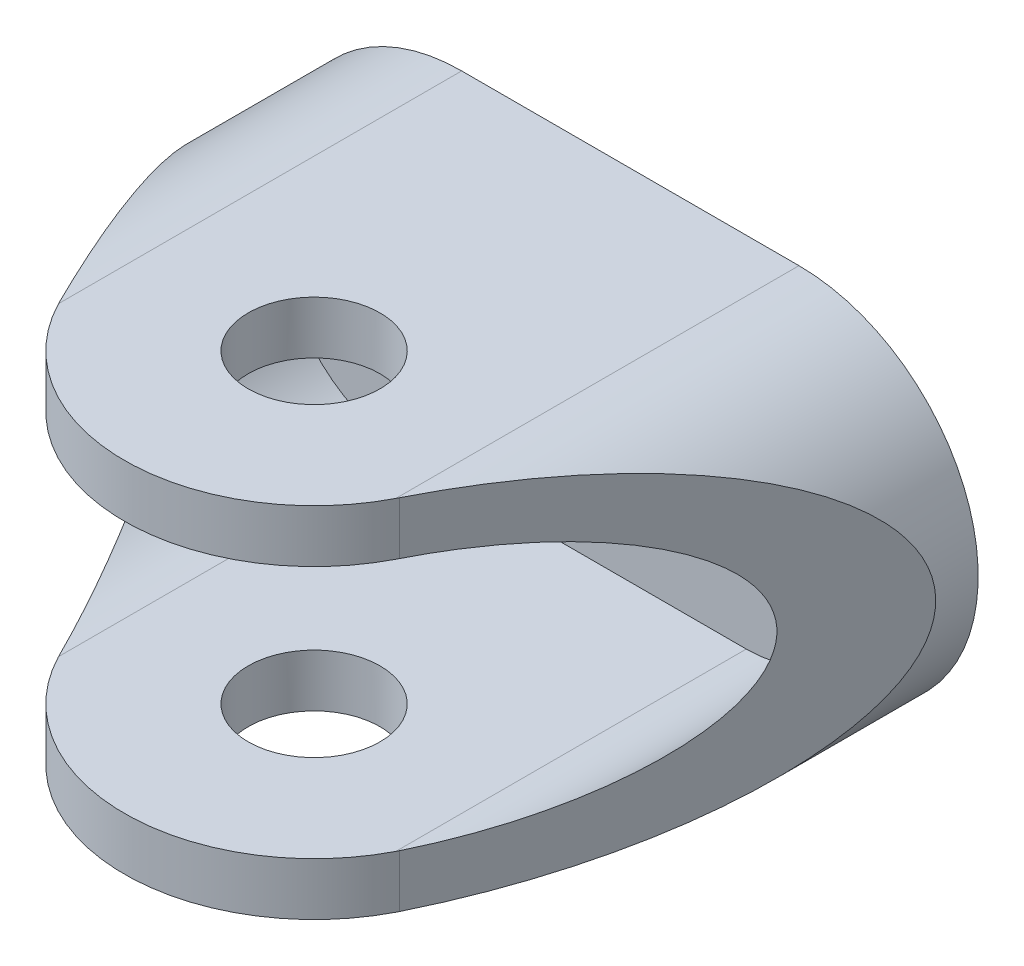
SolidWorks part; units mm, degrees
note: '?' marks a value the reader was unsure of.
material "6061 Alloy"
ref_plane "Front Plane" through (0, 0, 0) normal (0, 0, 1) x (1, 0, 0)
ref_plane "Top Plane" through (0, 0, 0) normal (0, 1, 0) x (1, 0, 0)
ref_plane "Right Plane" through (0, 0, 0) normal (1, 0, 0) x (0, 0, -1)
sketch "Sketch1" plane through (0, 0, 0) normal (0, 1, 0) x (1, 0, 0)
  line L0 (-22.225, -15.875) -> (22.225, -15.875)
  line L1 (-22.225, -15.875) -> (-22.225, 15.875)
  line L2 (22.225, -15.875) -> (22.225, 15.875)
  line L3 (-22.225, 15.875) -> (22.225, 15.875)
  line L4 (-22.225, -15.875) -> (22.225, 15.875) construction
  line L5 (22.225, -15.875) -> (-22.225, 15.875) construction
  point P1 (0, 0)
  dimension "D1" = 31.75
  dimension "D2" = 44.45
extrude "Billet" add sketch "Sketch1" along normal blind 21.59
sketch "Sketch2" plane through (0, 21.59, 0) normal (0, 1, 0) x (1, 0, 0)
  line L1 (-10.2367, -8.2598) -> (-22.225, 15.875)
  line L4 (-22.225, 15.875) -> (22.225, 15.875) construction
  line L5 (0, -14.605) -> (0, -11.9174) construction
  line L6 (-22.225, 15.875) -> (-22.225, -15.875)
  line L7 (-22.225, -15.875) -> (22.225, -15.875)
  line L8 (22.225, -15.875) -> (22.225, 15.875)
  line L9 (10.2367, -8.2598) -> (22.225, 15.875)
  line L10 (22.225, 15.875) -> (-22.225, 15.875) construction
  arc A0 (10.2367, -8.2598) -> (-10.2367, -8.2598) centre (0, -3.175) cw
  circle A1 centre (0, -3.175) radius 3.9688
  dimension "D1" = 11.43
  dimension "D3" = 7.9375
  dimension "D4" = 19.05
extrude "Mill Cut 1" cut sketch "Sketch2" against normal through all
ref_plane "Plane2" through (0, 21.59, 14.605) normal (0, 0, 1) x (1, 0, 0)
sketch "Sketch6" plane through (0, 21.59, 14.605) normal (0, 0, 1) x (1, 0, 0)
  line L0 (10.2367, 0) -> (-10.2367, 0) construction
  line L1 (-10.16, -3.175) -> (10.16, -3.175)
  line L3 (-10.16, -18.415) -> (10.16, -18.415)
  line L5 (0, -3.175) -> (0, 0) construction
  line L6 (0, -18.415) -> (0, -21.59) construction
  arc A0 (-10.16, -3.175) -> (-10.16, -18.415) centre (-10.16, -10.795) ccw
  arc A1 (10.16, -3.175) -> (10.16, -18.415) centre (10.16, -10.795) cw
  point P6 (0, 0)
  point P7 (0, -3.175)
  dimension "D1" = 3.175
  dimension "D2" = 10.16
extrude "Cut-Extrude1" cut sketch "Sketch6" against normal offset from surface (27.305 mm away) 3.175 up to face at (0, 10.795, -15.875)
sketch "Sketch8" plane through (0, 21.59, 14.605) normal (0, 0, 1) x (1, 0, 0)
  line L7 (-10.2367, 0) -> (-22.225, 0) construction
  line L8 (-10.16, -21.59) -> (-60.96, -21.59)
  line L9 (-60.96, -21.59) -> (-60.96, 0)
  line L10 (-60.96, 0) -> (-10.16, 0)
  line L11 (-10.2367, -21.59) -> (-22.225, -21.59) construction
  arc A4 (-10.16, 0) -> (-10.16, -21.59) centre (-10.16, -10.795) ccw
  arc A8 (-10.16, -3.175) -> (-10.16, -18.415) centre (-10.16, -10.795) ccw construction
  dimension "D1" = 50.8
extrude "Cut-Extrude2" cut sketch "Sketch8" against normal through all
mirror "Mirror1" about plane through (0, 0, 0) normal (1, 0, 0) of "Cut-Extrude2"
sketch "Sketch9" plane through (0, 0, -12.7) normal (0, 0, 1) x (1, 0, 0)
  line L0 (0, 21.59) -> (0, 0) construction
  line L1 (10.16, 21.59) -> (-10.16, 21.59) construction
  line L2 (0, 10.795) -> (12.7, 10.795) construction
  circle A0 centre (12.7, 10.795) radius 3.175
  circle A1 centre (-12.7, 10.795) radius 3.175
  dimension "D1" = 6.35
  dimension "D2" = 12.7
extrude "Holes" cut sketch "Sketch9" against normal through all
ref_axis "Axis1" [suppressed] through (0, -0.2051, 3.175) along (0, 1, 0)?
ref_plane "Plane1" [suppressed] through (0, 10.795, 0) normal (0, -1, 0) x (-1, 0, 0)
ref_plane "Horizontal Load" [suppressed] through (0.0554, 0, 3.174) normal (0.0175, 0, 0.9998) x (0, 1, 0)
ref_point "Point2" [suppressed]
ref_axis "Axis2" [suppressed] through (-11.1743, 10.795, 3.37) along (0.9998, 0, -0.0175)?
ref_plane "SUS Travel Load" [suppressed] through (0.0713, 0.3576, 4.087) normal (0.0174, 0.0872, 0.996) x (0.9998, 0, -0.0175)
sketch "Sketch5" [suppressed] plane through (0, 21.59, 0) normal (0, 1, 0) x (1, 0, 0)
  circle A0 centre (0, -3.175) radius 3.9688
  circle A1 centre (0, -3.175) radius 3.9688 construction
extrude "Mock Bolt" [suppressed] add sketch "Sketch5" against normal through all
